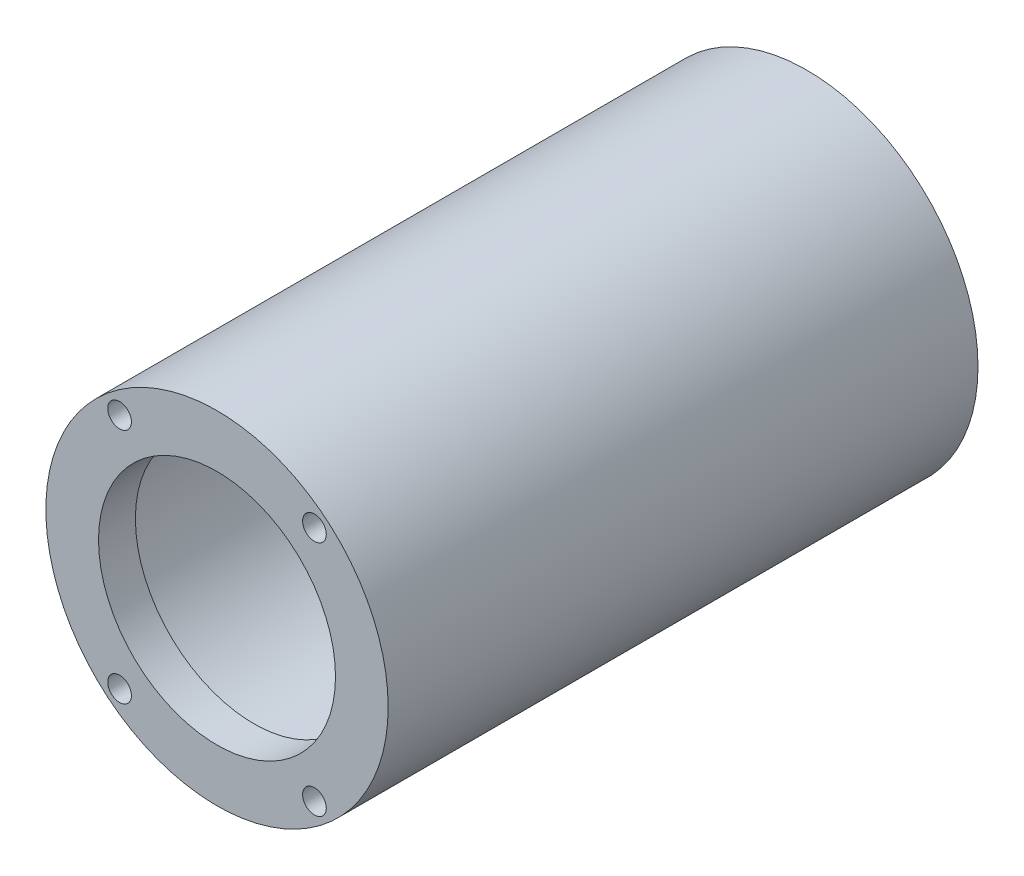
SolidWorks part; units mm, degrees
ref_plane "Alzado" through (0, 0, 0) normal (0, 0, 1) x (1, 0, 0)
ref_plane "Planta" through (0, 0, 0) normal (0, 1, 0) x (1, 0, 0)
ref_plane "Vista lateral" through (0, 0, 0) normal (1, 0, 0) x (0, 0, -1)
sketch "Croquis1" plane through (0, 0, 0) normal (0, 0, 1) x (1, 0, 0)
  circle A0 centre (0, 0) radius 32.5
  circle A1 centre (0, 0) radius 27.5
  dimension "D1" = 65
  dimension "D2" = 5
extrude "Boss-Extrude1" add sketch "Croquis1" along normal blind 112
sketch "Sketch1" plane through (0, 0, 0) normal (0, 0, -1) x (-1, 0, 0)
  line L0 (0, 0) -> (11.3818, 0) construction
  circle A0 centre (-30, 0) radius 1.5
  circle A1 centre (0, 30) radius 1.5
  circle A2 centre (30, 0) radius 1.5
  circle A3 centre (0, -30) radius 1.5
  circle A7 centre (0, 0) radius 30 construction
  circle A8 centre (0, 0) radius 27.5 construction
  point P17 (0, 0)
  dimension "D1" = 2.5
  dimension "D2" = 3
  dimension "D3" = 0
  dimension "D4" = 4
extrude "Cut-Extrude1" cut sketch "Sketch1" against normal blind 5
sketch "Sketch3" plane through (0, 0, 112) normal (0, 0, 1) x (1, 0, 0)
  circle A0 centre (0, 0) radius 27.5
  circle A2 centre (0, 0) radius 22.5
  circle A3 centre (0, 0) radius 27.5 construction
  dimension "D1" = 5
extrude "Boss-Extrude3" add sketch "Sketch3" against normal blind 7
sketch "Sketch2" plane through (0, 0, 112) normal (0, 0, 1) x (1, 0, 0)
  circle A0 centre (-18.5, 22.5) radius 2.25
  circle A1 centre (18.5, 22.5) radius 2.25
  circle A2 centre (18.5, -22.5) radius 2.25
  circle A3 centre (-18.5, -22.5) radius 2.25
  point P8 (0, 0)
  point P9 (0, 0)
  point P10 (0, 0)
  point P11 (0, 0)
  point P12 (18.5, -22.5)
  dimension "D5" = 4.5
  dimension "D6" = 4.5
  dimension "D7" = 4.5
  dimension "D8" = 4.5
  dimension "D1" = 37
  dimension "D2" = 45
  dimension "D3" = 18.5
  dimension "D4" = 22.5
extrude "Cut-Extrude2" cut sketch "Sketch2" against normal blind 5
equation "\"D3@Sketch2\"=\"D1@Sketch2\"/2"
equation "\"D4@Sketch2\"=\"D2@Sketch2\"/2"
equation "\"D6@Sketch2\"=\"D5@Sketch2\""
equation "\"D7@Sketch2\"=\"D5@Sketch2\""
equation "\"D8@Sketch2\"=\"D5@Sketch2\""
